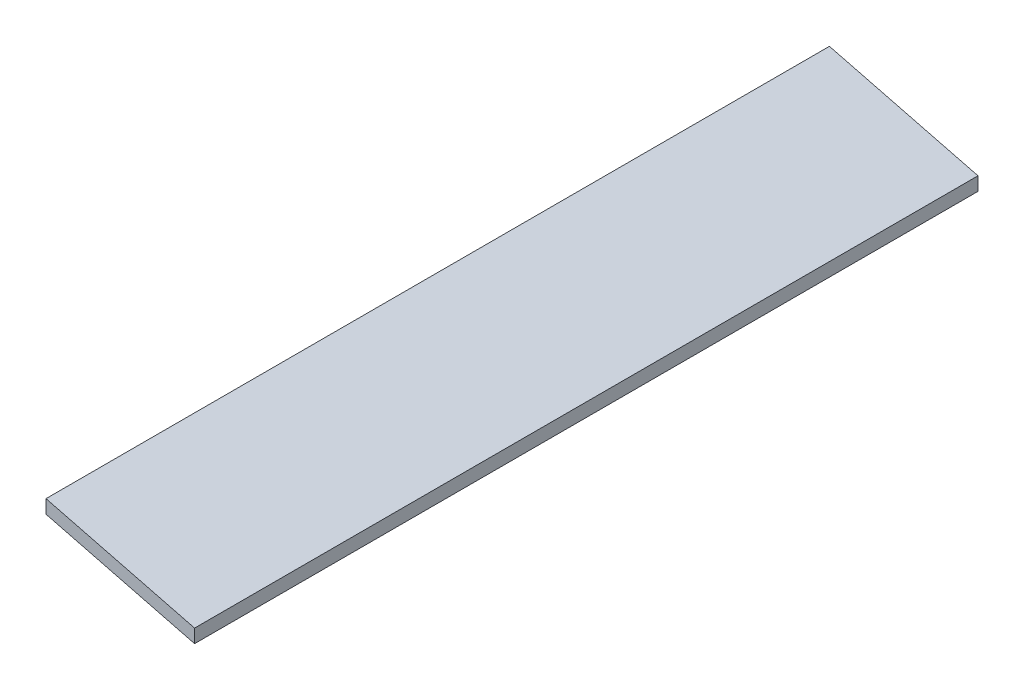
SolidWorks part; units mm, degrees
ref_plane "Plan de face" through (0, 0, 0) normal (0, 0, 1) x (1, 0, 0)
ref_plane "Plan de dessus" through (0, 0, 0) normal (0, 1, 0) x (1, 0, 0)
ref_plane "Plan de droite" through (0, 0, 0) normal (1, 0, 0) x (0, 0, -1)
sketch "Esquisse1" plane through (0, 0, 0) normal (0, 0, 1) x (1, 0, 0)
  line L0 (120, 155) -> (10, 183)
  line L1 (10, 183) -> (10, 173)
  line L2 (10, 183) -> (10, 0) construction
  line L3 (10, 173) -> (120, 145)
  line L4 (120, 0) -> (120, 155) construction
  line L5 (120, 145) -> (120, 155)
  dimension "D1" = 10
extrude "Boss.-Extru.1" add sketch "Esquisse1" against normal blind 580
